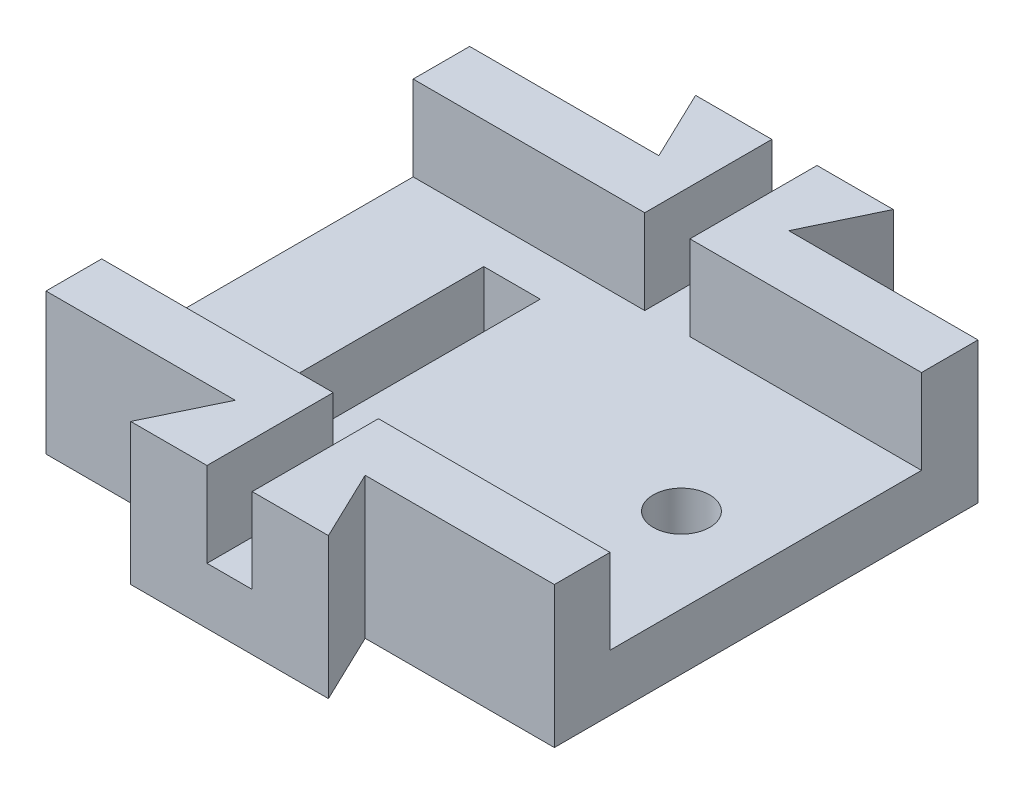
SolidWorks part; units mm, degrees
ref_plane "Front Plane" through (0, 0, 0) normal (0, 0, 1) x (1, 0, 0)
ref_plane "Top Plane" through (0, 0, 0) normal (0, 1, 0) x (1, 0, 0)
ref_plane "Right Plane" through (0, 0, 0) normal (1, 0, 0) x (0, 0, -1)
sketch "Sketch1" plane through (0, 0, 0) normal (0, 1, 0) x (1, 0, 0)
  line L1 (-59.3211, 124.9321) -> (120.6789, 124.9321)
  line L2 (-59.3211, 124.9321) -> (-59.3211, -25.0679)
  line L3 (-59.3211, -25.0679) -> (120.6789, -25.0679)
  line L4 (120.6789, 124.9321) -> (120.6789, -25.0679)
  line L5 (-19.3211, 9.9321) -> (0.6789, 9.9321)
  line L6 (-19.3211, 9.9321) -> (-19.3211, 89.9321)
  line L7 (-19.3211, 89.9321) -> (0.6789, 89.9321)
  line L8 (0.6789, 9.9321) -> (0.6789, 89.9321)
  dimension "D1" = 35
  dimension "D2" = 35
  dimension "D3" = 40
extrude "Boss-Extrude1" add sketch "Sketch1" along normal blind 50
shell "Shell1" thickness 20 removed face at (30.6789, 50, -49.9321)
sketch "Sketch3" plane through (0, 0, 0) normal (0, -1, 0) x (-1, 0, 0)
sketch "Sketch4" plane through (0, 50, 0) normal (0, 1, 0) x (1, 0, 0)
  line L0 (-39.3211, -5.0679) -> (-39.3211, 104.9321)
  line L1 (-39.3211, 104.9321) -> (20.6789, 104.9321)
  line L2 (20.6789, 104.9321) -> (20.6789, -5.0679)
  line L3 (20.6789, -5.0679) -> (-39.3211, -5.0679)
  line L4 (20.6789, -5.0679) -> (100.6789, -5.0679) construction
extrude "Cut-Extrude1" cut sketch "Sketch4" against normal blind 30
sketch "Sketch5" plane through (0, 0, 0) normal (0, -1, 0) x (1, 0, 0)
  line L0 (30.6789, 25.0679) -> (7.6789, 25.0679)
  line L1 (-59.3211, 25.0679) -> (120.6789, 25.0679) construction
  line L2 (7.6789, 25.0679) -> (-4.3211, 50.0679)
  line L3 (-4.3211, 50.0679) -> (65.6789, 50.0679)
  line L4 (65.6789, 50.0679) -> (53.6789, 25.0679)
  line L5 (53.6789, 25.0679) -> (30.6789, 25.0679)
  line L7 (19.067, 29.7324) -> (61.7771, 29.7324)
  line L8 (61.7771, 29.7324) -> (73.0332, 45.955)
  line L9 (73.0332, 45.955) -> (10.5603, 45.955)
  line L10 (10.5603, 45.955) -> (19.067, 29.7324)
  point P11 (0, 50.0679)
  point P12 (0, 50.0679)
  dimension "D1" = 23
  dimension "D2" = 23
  dimension "D3" = 25
  dimension "D4" = 25
  dimension "D5" = 55
  dimension "D6" = 55
extrude "Boss-Extrude2" add sketch "Sketch5" against normal blind 50 contours L3 L4 L5 L0 L2
sketch "Sketch6" plane through (0, 50, 0) normal (0, 1, 0) x (1, 0, 0)
  line L0 (22.6789, -50.0679) -> (22.6789, -5.0679)
  line L1 (-4.3211, -50.0679) -> (65.6789, -50.0679) construction
  line L2 (-39.3211, -5.0679) -> (100.6789, -5.0679) construction
  line L3 (22.6789, -5.0679) -> (38.6789, -5.0679)
  line L4 (38.6789, -5.0679) -> (38.6789, -50.0679)
  line L5 (38.6789, -50.0679) -> (22.6789, -50.0679)
  dimension "D1" = 15
  dimension "D2" = 15
extrude "Cut-Extrude2" cut sketch "Sketch6" against normal blind 30
ref_plane "Plane1" through (0, 0, -49.9321) normal (0, 0, 1) x (1, 0, 0)
mirror "Mirror1" about plane through (0, 0, -49.9321) normal (0, 0, 1) of "Cut-Extrude2", "Boss-Extrude2"
sketch "Sketch7" plane through (0, 0, 0) normal (0, -1, 0) x (-1, 0, 0)
  line L0 (-90.6789, 124.9321) -> (-90.6789, -25.0679) construction
  line L1 (-120.6789, 124.9321) -> (-53.6789, 124.9321) construction
  line L2 (-53.6789, -25.0679) -> (-120.6789, -25.0679) construction
  line L3 (-90.6789, 49.9321) -> (-120.6789, 49.9321) construction
  line L4 (-120.6789, -25.0679) -> (-120.6789, 124.9321) construction
  circle A0 centre (-90.6789, 49.9321) radius 10
extrude "Cut-Extrude3" cut sketch "Sketch7" against normal blind 28 contours A0
sketch "Sketch8" plane through (120.6789, 0, 0) normal (1, 0, 0) x (0, 0, -1)
  line L0 (104.9321, 50) -> (104.9321, 20)
  line L1 (-25.0679, 50) -> (124.9321, 50) construction
  line L2 (104.9321, 20) -> (-5.3609, 20)
  line L3 (-5.3609, 20) -> (-5.3609, 50)
  line L4 (-5.3609, 50) -> (104.9321, 50)
extrude "Cut-Extrude4" cut sketch "Sketch8" against normal blind 213
sketch "Sketch9" plane through (0, 0, 0) normal (0, -1, 0) x (1, 0, 0)
  line L0 (41.4838, -66.6169) -> (12.9499, -66.6169)
  line L1 (12.9499, -66.6169) -> (22.2361, -57.3306)
  line L2 (22.2361, -57.3306) -> (50.77, -57.3306)
  line L3 (50.77, -57.3306) -> (41.4838, -66.6169)
  line L4 (31.6889, -55.2653) -> (31.6889, -45.4704)
  line L5 (31.6889, -45.4704) -> (40.9752, -36.1841)
  line L6 (40.9752, -36.1841) -> (50.77, -36.1841)
  line L7 (50.77, -36.1841) -> (31.6889, -55.2653)
  line L8 (38.7685, -36.1841) -> (22.2361, -36.1841)
  line L9 (22.2361, -36.1841) -> (12.9499, -45.4704)
  line L10 (12.9499, -45.4704) -> (29.4822, -45.4704)
  line L11 (29.4822, -45.4704) -> (38.7685, -36.1841)
extrude "Cut-Extrude5" cut sketch "Sketch9" against normal blind 2 contours L7 L6 L5 L4 | L10 L11 L8 L9 | L0 L1 L2 L3 region at (39.0626, 0, -43.5578) region at (25.8592, 0, -40.8273)
